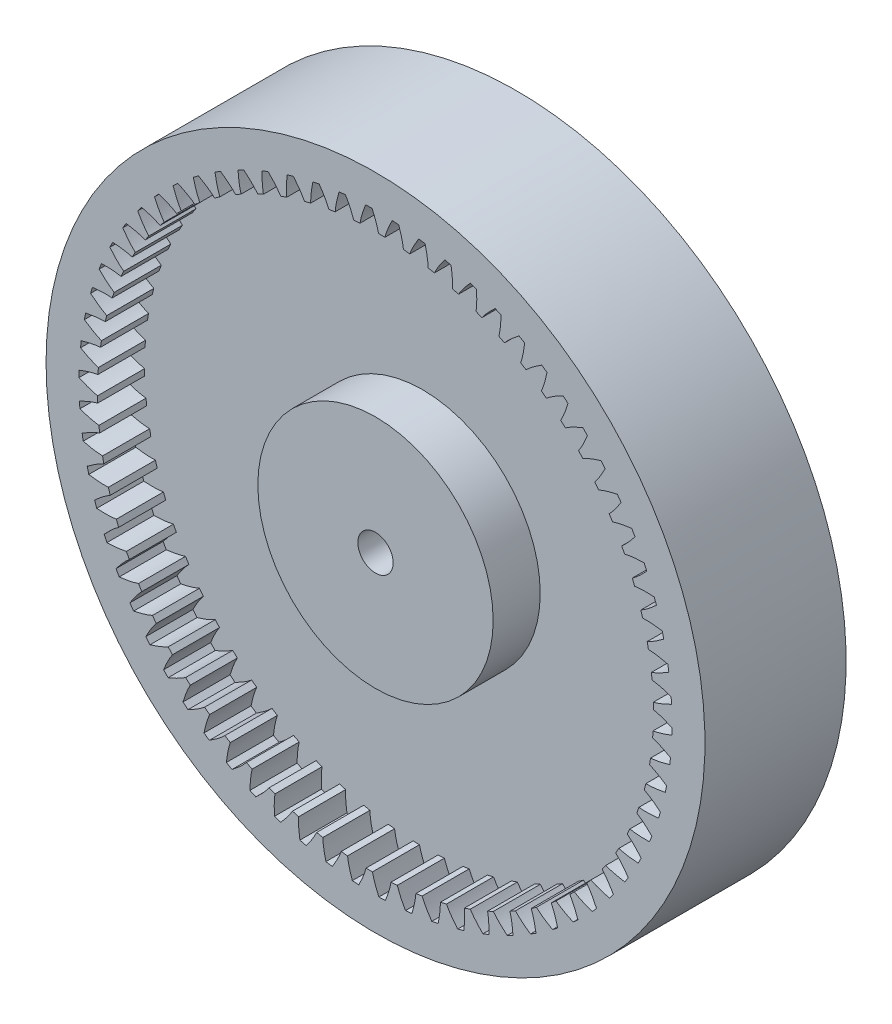
SolidWorks part; units mm, degrees
ref_plane "Front Plane" through (0, 0, 0) normal (0, 0, 1) x (1, 0, 0)
ref_plane "Top Plane" through (0, 0, 0) normal (0, 1, 0) x (1, 0, 0)
ref_plane "Right Plane" through (0, 0, 0) normal (1, 0, 0) x (0, 0, -1)
sketch "Sketch1" plane through (0, 0, 0) normal (1, 0, 0) x (0, 0, -1)
  line L0 (0, 0) -> (-86.9368, 0) construction
  line L1 (-15, 0) -> (-15, 70)
  line L5 (15, 70) -> (-15, 70)
  line L7 (-15, 0) -> (15, 0)
  line L9 (15, 70) -> (15, 0)
  point P6 (0, 0)
  dimension "D1" = 140
  dimension "D2" = 30
revolve "Revolve1" add sketch "Sketch1" angle 360 about L0
sketch "Sketch2" plane through (0, 0, 15) normal (0, 0, 1) x (1, 0, 0)
  line L0 (0, 0) -> (0, 61.25) construction
  line L1 (0, 61.25) -> (-19.6854, 54.0851)
  line L2 (-19.6854, 54.0851) -> (0, 0) construction
  circle A0 centre (0, 0) radius 59.0625 construction
  circle A1 centre (0, 0) radius 61.25 construction
  circle A2 centre (0, 0) radius 63 construction
  circle A3 centre (0, 0) radius 57.5562 construction
  arc A4 (0.8578, 57.5498) -> (-19.6854, 54.0851) centre (0, 0) ccw
  dimension "D1" = 122.5
  dimension "D2" = 126
  dimension "D3" = 118.125
  dimension "D4" = 20
sketch "Sketch3" plane through (0, 0, 15) normal (0, 0, 1) x (1, 0, 0)
  line L0 (0, 61.25) -> (-19.6854, 54.0851) construction
  line L1 (0, 61.25) -> (-19.6854, 54.0851)
  line L2 (-9.5718, 56.7547) -> (0.7567, 58.4966) construction
  line L3 (-29.1487, 49.6293) -> (-2.0534, 65.5432) construction
  line L4 (-37.6494, 43.5343) -> (-5.959, 70.9408) construction
  line L5 (-44.9066, 36.0015) -> (-12.1479, 76.8632) construction
  arc A0 (-19.6854, 54.0851) -> (-29.1487, 49.6293) centre (0, 0) ccw
  arc A1 (0.8578, 57.5498) -> (-9.5718, 56.7547) centre (0, 0) ccw
  arc A2 (-9.5718, 56.7547) -> (-19.6854, 54.0851) centre (0, 0) ccw
  arc A3 (-29.1487, 49.6293) -> (-37.6494, 43.5343) centre (0, 0) ccw
  arc A4 (-37.6494, 43.5343) -> (-44.9066, 36.0015) centre (0, 0) ccw
  circle A5 centre (0, 0) radius 57.5562 construction
  dimension "D2" = 10.4744
  dimension "D3" = 20.9487
  dimension "D4" = 31.4231
  dimension "D5" = 41.8975
  dimension "D6" = 52.3718
  dimension "D1" = 10.4744
sketch "Sketch4" plane through (0, 0, 15) normal (0, 0, 1) x (1, 0, 0)
  line L0 (0, 0) -> (-0.8316, 37.0522) construction
  line L1 (0, 0) -> (0, 61.25) construction
  arc A0 (-3.3019, 58.9701) -> (0.6529, 59.0589) centre (0, 0) cw
  circle A1 centre (0, 0) radius 59.0625 construction
  arc A2 (-2.104, 62.9649) -> (-0.7231, 62.9959) centre (0, 0) cw
  circle A4 centre (0, 0) radius 63 construction
  spline S0 degree 3 poles (-12.1479, 76.8632) (-8.2295, 73.6844) (-3.4906, 68.7515) (0.0079, 61.5983) (0.7887, 58.8211) (0.8578, 57.5498) knots 0 0 0 0 0.639984 0.839981 1 1 1 1
  spline S1 degree 3 poles (8.6872, 77.3308) (4.9154, 73.9794) (0.4026, 68.8388) (-2.7715, 61.5359) (-3.4269, 58.7265) (-3.4389, 57.4533) knots 0 0 0 0 0.639984 0.839981 1 1 1 1
  dimension "D1" = 1.286
sketch "Sketch5" plane through (0, 0, 15) normal (0, 0, 1) x (1, 0, 0)
  circle A0 centre (0, 0) radius 59.0625 construction
  circle A1 centre (0, 0) radius 59.0625
extrude "Cut-Extrude1" cut sketch "Sketch5" against normal blind 10
extrude "Cut-Extrude2" cut sketch "Sketch4" against normal blind 10 contours A2 S1 A0 S0 region at (-1.3625, 60.7071, 15)
pattern_circular "CirPattern1" count 70 over 360 about axis through (0, 0, 5) along (0, 0, 1) of "Cut-Extrude2"
sketch "Sketch6" plane through (0, 0, 5) normal (0, 0, 1) x (1, 0, 0)
  circle A0 centre (0, 0) radius 25
  dimension "D1" = 50
extrude "Boss-Extrude1" add sketch "Sketch6" along normal blind 10
sketch "Sketch8" plane through (0, 0, 15) normal (0, 0, 1) x (1, 0, 0)
  circle A0 centre (0, 0) radius 3.75
  dimension "D1" = 7.5
extrude "Cut-Extrude3" cut sketch "Sketch8" against normal through all
equation "\"D1@Sketch2\"=\"PD\""
equation "\"D2@Sketch2\"=\"D1@Sketch2\"+\"Addendum\"*2"
equation "\"D3@Sketch2\"=\"D1@Sketch2\"-\"Dedendum\"*2"
equation "\"D2@Sketch3\"=\"D3@Sketch3\"-\"D1@Sketch3\""
equation "\"D4@Sketch3\"=\"D3@Sketch3\"+\"D1@Sketch3\""
equation "\"D5@Sketch3\"=\"D4@Sketch3\"+\"D1@Sketch3\""
equation "\"D6@Sketch3\"=\"D5@Sketch3\"+\"D1@Sketch3\""
equation "\"D1@Sketch4\"=90/\"Teeth\""
equation "\"D1@CirPattern1\"=\"Teeth\""
equation "\"Teeth\" = 70"
equation "\"Module\"= 1.75mm"
equation "\"PD\"= \"Module\" * \"Teeth\""
equation "\"Addendum\"= \"Module\""
equation "\"Dedendum\"= \"Module\" * 1.25"
